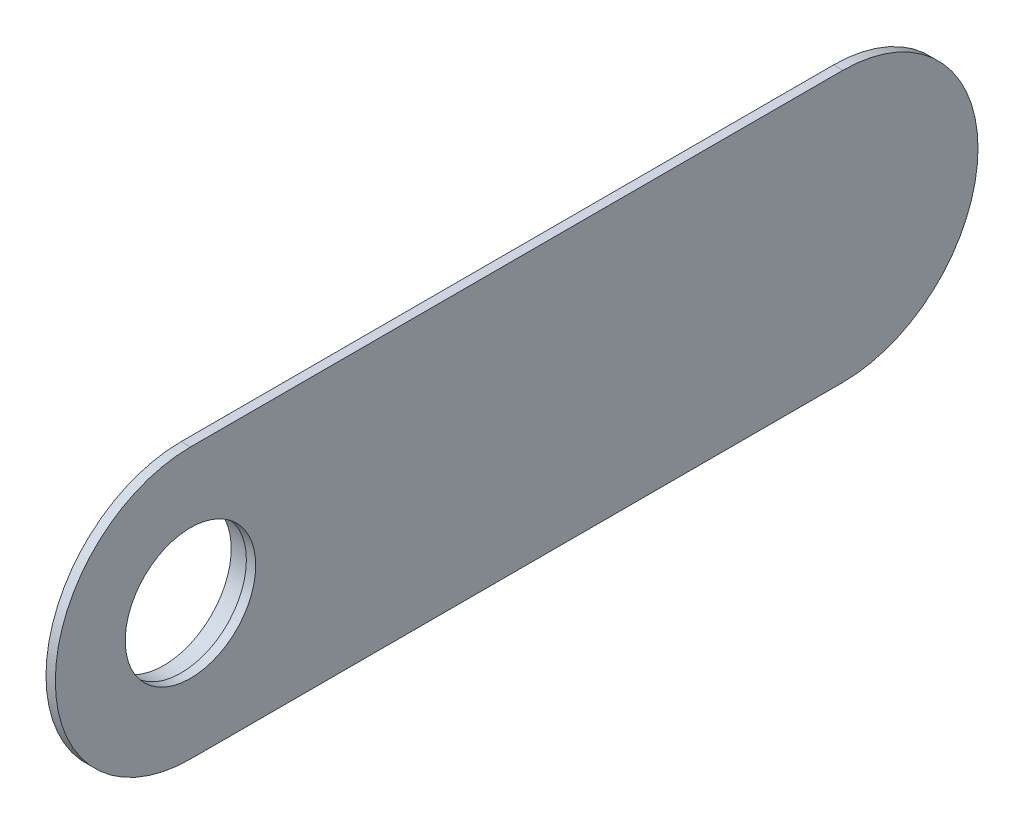
SolidWorks part; units mm, degrees
ref_plane "Front Plane" through (0, 0, 0) normal (0, 0, 1) x (1, 0, 0)
ref_plane "Top Plane" through (0, 0, 0) normal (0, 1, 0) x (1, 0, 0)
ref_plane "Right Plane" through (0, 0, 0) normal (1, 0, 0) x (0, 0, -1)
sketch "Sketch1" plane through (0, 0, 0) normal (1, 0, 0) x (0, 0, -1)
  line L0 (0, 0) -> (280, 0) construction
  line L1 (0, 58) -> (280, 58)
  line L2 (0, -58) -> (280, -58)
  arc A0 (0, 58) -> (0, -58) centre (0, 0) ccw
  arc A1 (280, -58) -> (280, 58) centre (280, 0) ccw
  circle A2 centre (0, 0) radius 28
  point P3 (140, 0)
  dimension "D2" = 58
  dimension "D3" = 56
  dimension "D1" = 280
extrude "Boss-Extrude1" add sketch "Sketch1" along normal blind 4
ref_plane "Plane1" through (-7.5, 0, 0) normal (-1, 0, 0) x (0, 0, 1)
sketch "Sketch2" plane through (-7.5, 0, 0) normal (-1, 0, 0) x (0, 0, 1)
  circle A0 centre (0, 0) radius 29
  circle A1 centre (0, 0) radius 35
  dimension "D1" = 58
  dimension "D2" = 70
extrude "Boss-Extrude2" add sketch "Sketch2" against normal up to surface (7.5 mm away) up to face at (0, 0, -140)
chamfer "Chamfer1" distance 8 angle 45 1 edges at (0, 0, -35)
